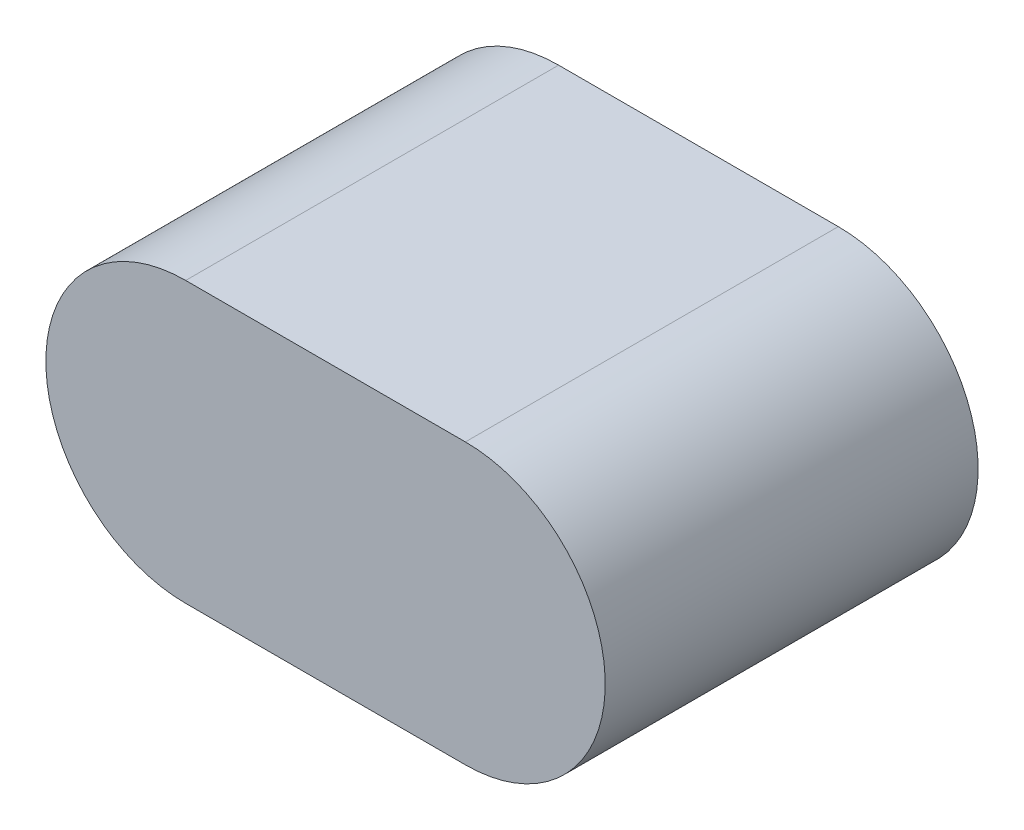
SolidWorks part; units mm, degrees
ref_plane "前视基准面" through (0, 0, 0) normal (0, 0, 1) x (1, 0, 0)
ref_plane "上视基准面" through (0, 0, 0) normal (0, 1, 0) x (1, 0, 0)
ref_plane "右视基准面" through (0, 0, 0) normal (1, 0, 0) x (0, 0, -1)
sketch "草图1" plane through (0, 0, 0) normal (0, 1, 0) x (1, 0, 0)
  line L0 (-150, 100) -> (150, 100)
  line L5 (150, 100) -> (150, -100)
  line L8 (-150, 100) -> (-150, -100)
  line L9 (-150, -100) -> (150, -100)
extrude "凸台-拉伸1" add sketch "草图1" along normal blind 75 and the other way blind 75
sketch "草图2" plane through (0, 0, 0) normal (0, 0, 1) x (1, 0, 0)
  line L2 (-150, 75) -> (150, 75) construction
  line L3 (-150, -75) -> (150, -75) construction
  line L4 (-75, 75) -> (75, 75)
  line L6 (-75, -75) -> (75, -75)
  arc A0 (-75, 75) -> (-75, -75) centre (-75, 0) ccw
  arc A1 (75, 75) -> (75, -75) centre (75, 0) cw
  point P3 (0, -75)
extrude "切除-拉伸2" cut sketch "草图2" against normal through all and the other way through all flip side to cut
